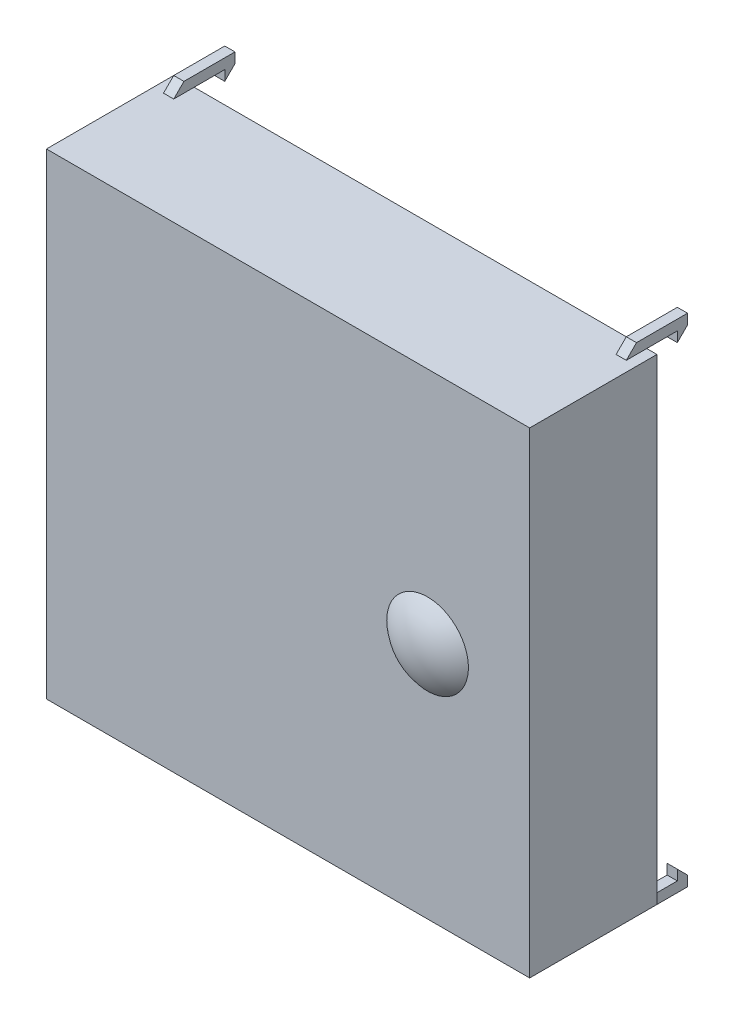
SolidWorks part; units mm, degrees
ref_plane "Front Plane" through (0, 0, 0) normal (0, 0, 1) x (1, 0, 0)
ref_plane "Top Plane" through (0, 0, 0) normal (0, 1, 0) x (1, 0, 0)
ref_plane "Right Plane" through (0, 0, 0) normal (1, 0, 0) x (0, 0, -1)
sketch "Sketch1" plane through (0, 0, 0) normal (0, 0, 1) x (1, 0, 0)
  line L0 (10.75, -9.75) -> (-121.1, -9.75) construction
  line L1 (10.75, 60.25) -> (-60.25, 60.25)
  line L2 (10.75, 60.25) -> (10.75, -9.75)
  line L3 (10.75, -9.75) -> (-60.25, -9.75)
  line L4 (-60.25, 60.25) -> (-60.25, -9.75)
  line L5 (9.25, 58.75) -> (-58.75, 58.75)
  line L6 (-58.75, 58.75) -> (-58.75, -8.25)
  line L7 (9.25, -8.25) -> (-58.75, -8.25)
  line L8 (9.25, 58.75) -> (9.25, -8.25)
  dimension "D1" = 71
  dimension "D2" = 1.5
extrude "Boss-Extrude1" add sketch "Sketch1" along normal blind 17.2
extrude "Boss-Extrude2" add sketch "Sketch1<2>" along normal blind 1.5 from surface contours L4 L3 L2 L1 starting at face at (-24.75, 25.25, 17.2)
sketch "Sketch1<2>" plane through (0, 0, 0) normal (0, 0, 1) x (1, 0, 0) same geometry as "Sketch1"
sketch "Sketch3" plane through (0, 60.25, 0) normal (0, 1, 0) x (1, 0, 0)
  line L0 (-58.75, -3) -> (-60.25, -3) construction
  line L1 (-58.75, -3) -> (-57.25, -3)
  line L2 (-58.75, -3) -> (-58.75, 0)
  line L3 (-58.75, 0) -> (-57.25, 0)
  line L4 (-57.25, -3) -> (-57.25, 0)
  line L5 (-60.25, -18.7) -> (-60.25, 0) construction
  line L6 (10.75, 0) -> (-121.1, 0) construction
  dimension "D1" = 1.5
  dimension "D2" = 3
sketch "Sketch4" plane through (-60.25, 0, 0) normal (-1, 0, 0) x (0, 0, 1)
  line L0 (3, 60.25) -> (0, 60.25) construction
  line L1 (3, 60.25) -> (-4.5, 60.25)
  line L2 (0, -9.75) -> (0, 60.25) construction
  line L3 (1.5, 61.75) -> (-4.5, 61.75)
  line L4 (0, 60.25) -> (-36.6375, 60.25) construction
  line L5 (3, 60.25) -> (0, 60.25) construction
  line L6 (3, 60.25) -> (1.5, 61.75)
  line L7 (1.5, 61.75) -> (1.5, 60.25) construction
  line L8 (-36.6375, 58.75) -> (-32.3875, 58.75) construction
  line L9 (-4.5, 61.75) -> (-6, 61.75)
  line L10 (-4.5, 61.75) -> (-4.5, 58.75)
  line L12 (-6, 61.75) -> (-6, 60.25)
  line L13 (-4.5, 58.75) -> (-6, 60.25)
  line M12 (18.7, 60.25) -> (0, 60.25)
  dimension "D1" = 1.5
  dimension "D2" = 3
  dimension "D3" = 45
  dimension "D4" = 6
extrude "Boss-Extrude4" add sketch "Sketch4" against normal blind 1.5 from offset 1.5 contours L6 L7 M12 | L7 L3 L10 L1 | L13 L10 L9 L12 region at (-60.25, 60.75, 2) region at (-60.25, 61, -1.5) region at (-60.25, 60.5833, -5.1667) offset against normal yes
ref_plane "Plane1" through (0, 25.25, 0) normal (0, 1, 0) x (1, 0, 0)
ref_plane "Plane2" through (-24.75, 0, 0) normal (1, 0, 0) x (0, 0, -1)
mirror "Mirror1" about plane through (0, 25.25, 0) normal (0, 1, 0) of "Boss-Extrude4"
mirror "Mirror2" about plane through (-24.75, 0, 0) normal (1, 0, 0) of "Mirror1", "Boss-Extrude4"
ref_plane "Plane3" through (0, 0, 20.975) normal (0, 0, 1) x (1, 0, 0)
sketch "Sketch5" plane through (0, 0, 18.7) normal (0, 0, 1) x (1, 0, 0)
  line L0 (10.75, 60.25) -> (10.75, -9.75) construction
  line L1 (1.75, 25.25) -> (10.75, 25.25) construction
  circle A0 centre (-4.25, 25.25) radius 6
  point P4 (10.75, 25.25)
  dimension "D1" = 12
  dimension "D2" = 9
extrude "Boss-Extrude5" add sketch "Sketch5" along normal up to surface (2.275 mm away) up to plane "Plane3"
fillet "Fillet1" radius 9 1 edges at (1.75, 25.25, 20.975)
equation "\"D1@Boss-Extrude1\"=14.2+3"
